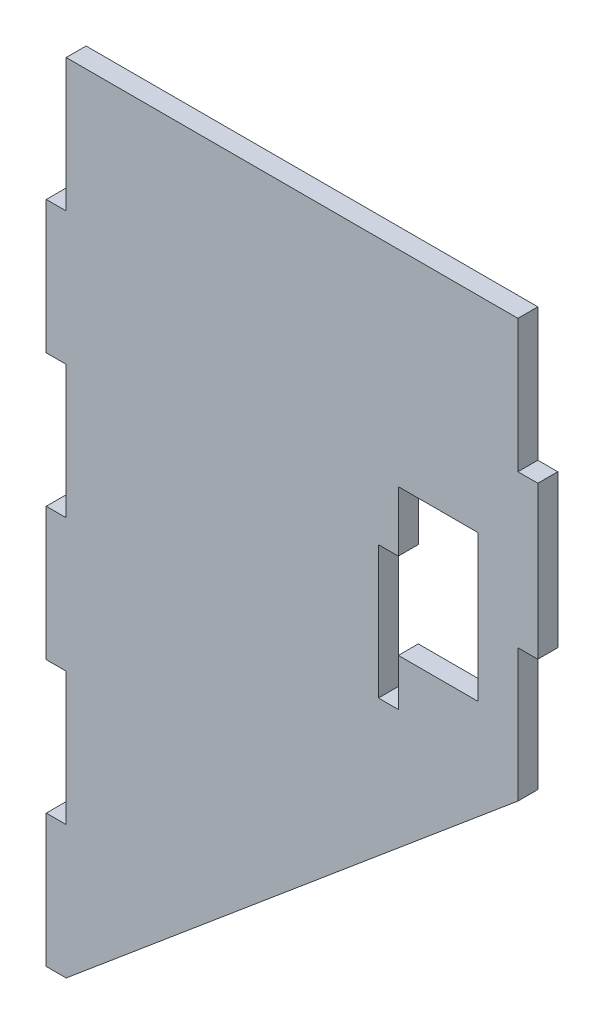
SolidWorks part; units mm, degrees
material "Acrilico TEC"
ref_plane "Front Plane" through (0, 0, 0) normal (0, 0, 1) x (1, 0, 0)
ref_plane "Top Plane" through (0, 0, 0) normal (0, 1, 0) x (1, 0, 0)
ref_plane "Right Plane" through (0, 0, 0) normal (1, 0, 0) x (0, 0, -1)
sketch "Sketch1" plane through (0, 0, 0) normal (0, 0, 1) x (1, 0, 0)
  line L0 (-3, 60) -> (-3, 40)
  line L1 (-3, 40) -> (0, 40)
  line L2 (0, 40) -> (0, 20)
  line L3 (0, 20) -> (-3, 20)
  line L4 (-3, 20) -> (-3, 0)
  line L5 (-3, 60) -> (0, 60)
  line L6 (0, 60) -> (0, 80)
  line L7 (0, 80) -> (-3, 80)
  line L8 (-3, 80) -> (-3, 100)
  line L9 (0, 120) -> (23.5, 120)
  line L10 (23.5, 120) -> (23.5, 105) construction
  line L11 (-3, 0) -> (0, 0)
  line L12 (23.5, 120) -> (68, 120)
  line L13 (68, 57.0588) -> (68, 77.0588)
  line L14 (47, 80) -> (50, 80)
  line L15 (47, 60) -> (47, 80)
  line L16 (50, 60) -> (47, 60)
  line L17 (68, 77.0588) -> (71, 77.0588)
  line L18 (71, 77.0588) -> (71, 100)
  line L19 (71, 100) -> (68, 100)
  line L20 (68, 100) -> (68, 120)
  line L21 (50, 89.0588) -> (62, 89.0588)
  line L22 (0, 0) -> (68, 57.0588)
  line L23 (0, 0) -> (3.8747, 0) construction
  line L24 (50, 89.0588) -> (50, 80)
  line L25 (50, 60) -> (50, 67.0588)
  line L26 (50, 67.0588) -> (62, 67.0588)
  line L27 (-3, 100) -> (0, 100)
  line L28 (0, 100) -> (0, 120)
  line L30 (62, 89.0588) -> (62, 67.0588)
  dimension "D2" = 12
  dimension "D3" = 20
  dimension "D4" = 23.5
  dimension "D5" = 20
  dimension "D6" = 3
  dimension "D7" = 22.9412
  dimension "D8" = 23.5
  dimension "D9" = 15
  dimension "D10" = 20
  dimension "D11" = 20
  dimension "D12" = 52.9412
  dimension "D13" = 40
  dimension "D14" = 20
  dimension "D15" = 3
  dimension "D16" = 22
  dimension "D17" = 3
  dimension "D20" = 40
extrude "Boss-Extrude1" add sketch "Sketch1" along normal blind 3
